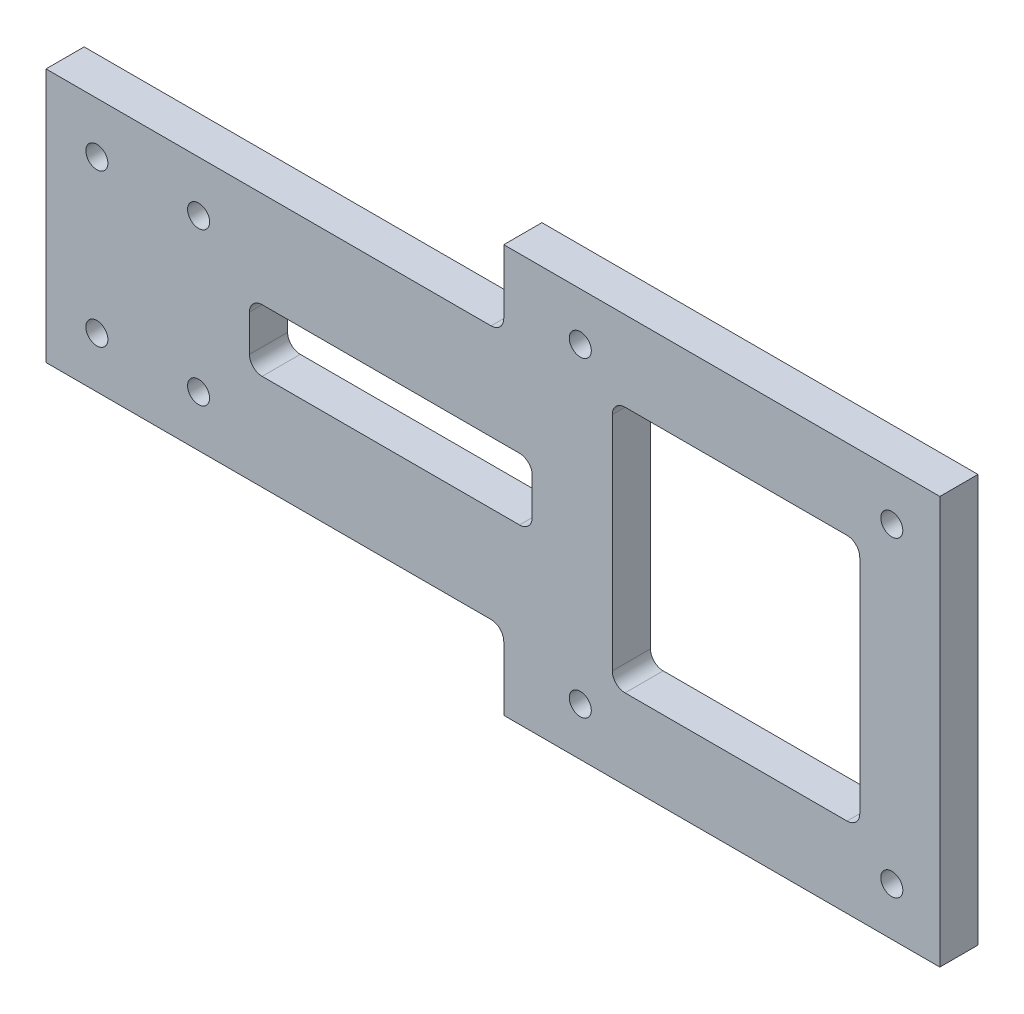
SolidWorks part; units mm, degrees
material "6061-T6 (SS)"
ref_plane "Front" through (0, 0, 0) normal (0, 0, 1) x (1, 0, 0)
ref_plane "Top" through (0, 0, 0) normal (0, 1, 0) x (1, 0, 0)
ref_plane "Right" through (0, 0, 0) normal (1, 0, 0) x (0, 0, -1)
sketch "Sketch1" plane through (0, 0, 0) normal (0, 0, 1) x (1, 0, 0)
  line L0 (82.55, 31.75) -> (82.55, 50.8909)
  line L1 (82.55, 31.75) -> (-31.75, 31.75)
  line L3 (82.55, -31.75) -> (-31.75, -31.75)
  line L4 (-31.75, 31.75) -> (-31.75, -31.75)
  line L5 (-31.75, -31.75) -> (0, 0) construction
  line L6 (0, 0) -> (-31.75, 31.75) construction
  line L7 (82.55, 50.8909) -> (191.4409, 50.8909)
  line L8 (191.4409, 50.8909) -> (191.4409, 30.8909)
  line L9 (191.4409, 30.8909) -> (109.6591, 30.8909)
  line L10 (109.6591, 30.8909) -> (109.6591, -30.8909)
  line L11 (109.6591, -30.8909) -> (191.4409, -30.8909)
  line L12 (191.4409, -30.8909) -> (191.4409, -50.8909)
  line L13 (191.4409, -50.8909) -> (82.55, -50.8909)
  line L14 (82.55, -50.8909) -> (82.55, -31.75)
  line L15 (179.4409, -30.8909) -> (179.4409, -38.8909) construction
  line L16 (179.4409, -38.8909) -> (179.4409, -50.8909) construction
  line L17 (0, 0) -> (140.55, 0) construction
  line L18 (179.4409, -38.8909) -> (101.6591, 38.8909) construction
  line L19 (179.4409, 38.8909) -> (101.6591, -38.8909) construction
  line L20 (109.6591, 30.8909) -> (140.55, 0) construction
  line L21 (140.55, 0) -> (109.6591, -30.8909) construction
  line L22 (179.4409, 38.8909) -> (179.4409, 50.8909) construction
  line L23 (179.4409, 38.8909) -> (191.4409, 38.8909) construction
  line L24 (179.4409, 38.8909) -> (179.4409, 30.8909) construction
  line L25 (101.6591, 38.8909) -> (82.55, 38.8909) construction
  line L26 (0, 0) -> (109.6591, 0) construction
  line L27 (0, 0) -> (82.55, -31.75) construction
  line L28 (0, 0) -> (82.55, 31.75) construction
  line L29 (179.4409, -38.8909) -> (191.4409, -38.8909) construction
  line L30 (140.55, 0) -> (140.55, 30.8909) construction
  line L31 (140.55, 0) -> (109.6591, 0) construction
  circle A0 centre (140.55, 0) radius 55 construction
  point P0 (0, 0)
  point P17 (179.4409, 38.8909)
  point P18 (179.4409, -38.8909)
  point P19 (101.6591, 38.8909)
  point P20 (101.6591, -38.8909)
  dimension "D2" = 110
  dimension "D1" = 63.5
  dimension "D3" = 90
  dimension "D5" = 8
  dimension "D6" = 12
  dimension "D7" = 114.3
  dimension "D9" = 58
  dimension "D10" = 0
extrude "Boss-Extrude1" add sketch "Sketch1" along normal blind 9.525
hole_wizard "M5 Clearance Hole1" positions "Sketch3" profile "Sketch4" hole size "M5" standard "ANSI Metric"
sketch "Sketch3" plane through (0, 0, 9.525) normal (0, 0, 1) x (1, 0, 0)
  line L0 (0, 0) -> (140.55, 0) construction
  line L2 (179.4409, -38.8909) -> (101.6591, 38.8909) construction
  line L4 (179.4409, 38.8909) -> (101.6591, -38.8909) construction
  line L6 (109.6591, 30.8909) -> (140.55, 0) construction
  line L7 (140.55, 0) -> (109.6591, -30.8909) construction
  line L8 (82.55, 31.75) -> (-31.75, 31.75) construction
  line L12 (82.55, -31.75) -> (82.55, -50.8909) construction
  circle A0 centre (140.55, 0) radius 55 construction
  point P0 (179.4409, 38.8909)
  point P2 (179.4409, -38.8909)
  point P4 (101.6591, 38.8909)
  point P6 (101.6591, -38.8909)
  dimension "D1" = 110
  dimension "D2" = 135
  dimension "D3" = 90
  dimension "D4" = 58
sketch "Sketch4" plane through (179.4409, 38.8909, 9.525) normal (1, 0, 0) x (0, -1, 0)
  line L0 (0, 0) -> (0, 20.4024)
  line L1 (0, 20.4024) -> (2.75, 18.75)
  line L2 (2.75, 18.75) -> (2.75, 0)
  line L5 (2.75, 0) -> (0, 0)
  line L10 (0, 20.4024) -> (-2.75, 18.75) construction
  line L11 (0, -6.35) -> (0, 107.95) construction
  dimension "Hole Dia." = 5.5
  dimension "Hole Depth" = 18.75
  dimension "Drill Angle" = 118
fillet "Fillet1" radius 3.175 4 edges at (109.6591, 30.8909, 4.7625) (109.6591, -30.8909, 4.7625) (82.55, -31.75, 4.7625) (82.55, 31.75, 4.7625)
hole_wizard "M5 Clearance Hole2" positions "Sketch5" profile "Sketch6" hole size "M5" standard "ANSI Metric"
sketch "Sketch5" plane through (0, 0, 9.525) normal (0, 0, 1) x (1, 0, 0)
  line L0 (-19.05, 19.05) -> (6.35, 19.05) construction
  line L1 (6.35, 19.05) -> (6.35, -19.05) construction
  line L2 (6.35, -19.05) -> (-19.05, -19.05) construction
  line L3 (-19.05, -19.05) -> (-19.05, 19.05) construction
  line L5 (79.375, 31.75) -> (-31.75, 31.75) construction
  line L9 (-31.75, -31.75) -> (-19.05, -19.05) construction
  line L11 (-19.05, 19.05) -> (-31.75, 31.75) construction
  point P0 (-19.05, 19.05)
  point P2 (6.35, 19.05)
  point P4 (6.35, -19.05)
  point P6 (-19.05, -19.05)
  dimension "D1" = 12.7
  dimension "D2" = 25.4
sketch "Sketch6" plane through (-19.05, 19.05, 9.525) normal (1, 0, 0) x (0, -1, 0)
  line L0 (0, 0) -> (0, 20.4024)
  line L1 (0, 20.4024) -> (2.75, 18.75)
  line L2 (2.75, 18.75) -> (2.75, 0)
  line L5 (2.75, 0) -> (0, 0)
  line L10 (0, 20.4024) -> (-2.75, 18.75) construction
  line L11 (0, -6.35) -> (0, 107.95) construction
  dimension "Hole Dia." = 5.5
  dimension "Hole Depth" = 18.75
  dimension "Drill Angle" = 118
sketch "Sketch7" plane through (0, 0, 9.525) normal (0, 0, 1) x (1, 0, 0)
  line L0 (6.35, 19.05) -> (6.35, 31.75) construction
  line L1 (89.6591, -7.75) -> (19.05, -7.75)
  line L2 (89.6591, -7.75) -> (89.6591, 7.75)
  line L3 (89.6591, 7.75) -> (19.05, 7.75)
  line L4 (19.05, -7.75) -> (19.05, 7.75)
  line L5 (89.6591, -7.75) -> (19.05, 7.75) construction
  line L6 (89.6591, 7.75) -> (19.05, -7.75) construction
  line L7 (109.6591, -27.7159) -> (109.6591, 27.7159) construction
  line L8 (79.375, 31.75) -> (-31.75, 31.75) construction
  line L9 (0, 0) -> (54.3546, 0) construction
  line L10 (6.35, 19.05) -> (19.05, 19.05) construction
  point P0 (54.3546, 0)
  dimension "D1" = 20
  dimension "D2" = 24
extrude "Cut-Extrude1" cut sketch "Sketch7" against normal through all
fillet "Fillet2" radius 3.175 4 edges at (89.6591, -7.75, 4.7625) (89.6591, 7.75, 4.7625) (19.05, 7.75, 4.7625) (19.05, -7.75, 4.7625)
sketch "Sketch8" plane through (0, 0, 9.525) normal (0, 0, 1) x (1, 0, 0)
  line L0 (112.8341, 30.8909) -> (191.4409, 30.8909) construction
  line L1 (191.4409, -30.8909) -> (171.4409, -30.8909)
  line L2 (191.4409, -30.8909) -> (191.4409, 30.8909)
  line L3 (191.4409, 30.8909) -> (171.4409, 30.8909)
  line L4 (171.4409, -30.8909) -> (171.4409, 30.8909)
  line L5 (191.4409, -50.8909) -> (191.4409, -30.8909) construction
extrude "Boss-Extrude2" add sketch "Sketch8" against normal up to surface (9.525 mm away) up to face at (54.3546, 0, 0)
fillet "Fillet3" radius 3.175 2 edges at (171.4409, -30.8909, 4.7625) (171.4409, 30.8909, 4.7625)
